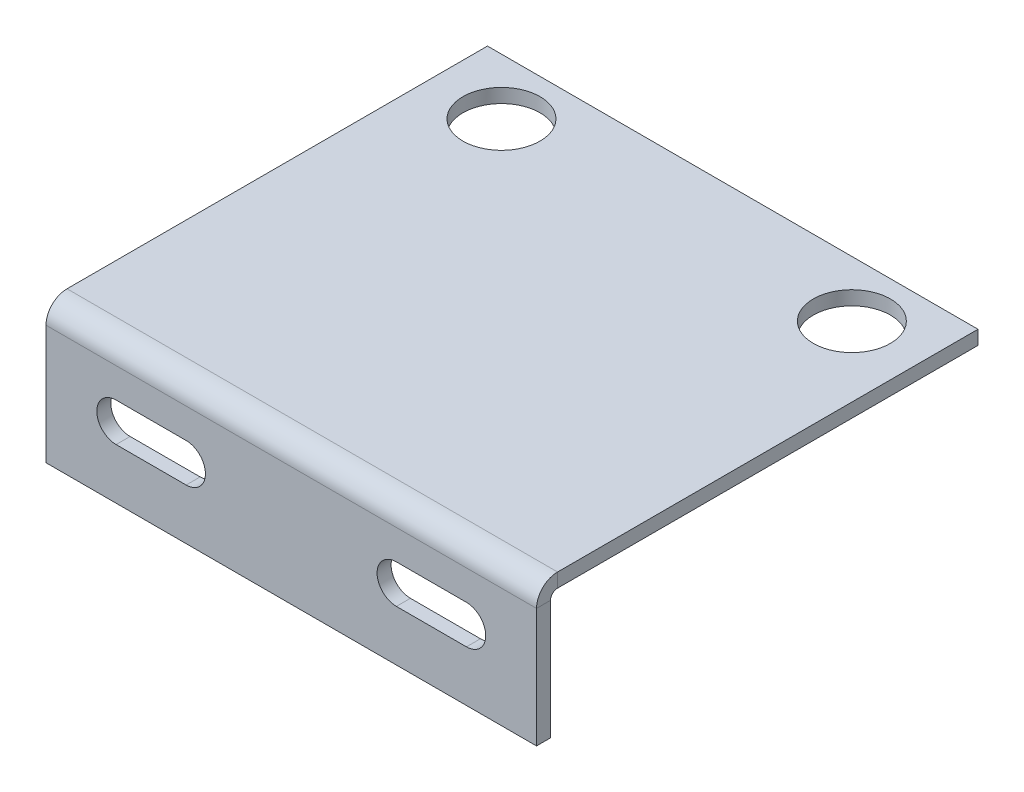
SolidWorks part; units mm, degrees
note: The reader was unsure of these and kept them because the rebuilt part matched: flange length of "边线-法兰1".
ref_plane "前视基准面" through (0, 0, 0) normal (0, 0, 1) x (1, 0, 0)
ref_plane "上视基准面" through (0, 0, 0) normal (0, 1, 0) x (1, 0, 0)
ref_plane "右视基准面" through (0, 0, 0) normal (1, 0, 0) x (0, 0, -1)
sketch "草图1" plane through (0, 0, 0) normal (0, 1, 0) x (1, 0, 0)
  line L1 (0, 0) -> (70, 0)
  line L2 (0, 0) -> (0, 60)
  line L3 (0, 60) -> (70, 60)
  line L4 (70, 0) -> (70, 60)
  dimension "D1" = 70
  dimension "D2" = 60
base flange "基体-法兰1" sketch "草图1" thickness 2 reverse thickness direction no parameters "D1"=1
edge flange "边线-法兰1" sketch "草图11" flange angle 90 flange length 20 flange position bend outside bend radius 1 thickness 2 relief rectangular parameters "D6"=10
bend "边线折弯1" bend radius 1 bend angle 90 parameters "D5"=1
sketch "草图11" plane through (0, -2, 0) normal (0, 0, 1) x (-1, 0, 0)
  line L0 (0, 0) -> (-70, 0) construction
  line L1 (0, 0) -> (-70, 0)
  line L2 (-70, 0) -> (-70, 18)
  line L3 (-70, 18) -> (0, 18)
  line L4 (0, 18) -> (0, 0)
sketch "草图12" plane through (0, 0, 1) normal (0, 0, -1) x (-1, 0, 0)
  line L0 (-55, -10) -> (-15, -10) construction
  line L1 (0, -20) -> (-70, -20) construction
  line L2 (-60, -10) -> (-50, -10) construction
  line L3 (-60, -7.25) -> (-50, -7.25)
  line L4 (-60, -12.75) -> (-50, -12.75)
  line L5 (-35, -10) -> (-35, -26.4916) construction
  line L6 (-10, -10) -> (-20, -10) construction
  line L7 (-10, -7.25) -> (-20, -7.25)
  line L8 (-10, -12.75) -> (-20, -12.75)
  arc A0 (-60, -7.25) -> (-60, -12.75) centre (-60, -10) ccw
  arc A1 (-50, -12.75) -> (-50, -7.25) centre (-50, -10) ccw
  arc A2 (-10, -7.25) -> (-10, -12.75) centre (-10, -10) cw
  arc A3 (-20, -12.75) -> (-20, -7.25) centre (-20, -10) cw
  point P2 (-35, -10)
  point P5 (-35, -20)
  point P8 (-55, -10)
  point P17 (-15, -10)
  dimension "D1" = 40
  dimension "D2" = 0
  dimension "D3" = 10
  dimension "D4" = 0
  dimension "D5" = 10
  dimension "D6" = 5.5
extrude "切除-拉伸1" cut sketch "草图12" against normal blind 10 normal cut yes
sketch "草图13" plane through (0, 0, 0) normal (0, 1, 0) x (1, 0, 0)
  line L0 (10, 52) -> (60, 52) construction
  line L1 (70, 60) -> (0, 60) construction
  circle A0 centre (10, 52) radius 5.5
  circle A1 centre (60, 52) radius 5.5
  point P4 (35, 52)
  point P5 (35, 60)
  dimension "D3" = 11
  dimension "D4" = 50
  dimension "D1" = 8
  dimension "D2" = 0
extrude "切除-拉伸2" cut sketch "草图13" against normal blind 10 normal cut yes
sketch "折弯-线1" plane through (0, 0, 0) normal (0, 1, 0) x (1, 0, 0)
sketch "边界框1" plane through (0, 0, 0) normal (0, 1, 0) x (1, 0, 0)
sheet metal parameters "钣金6" thickness 2 parameters "D1"=1
flat pattern "平板型式6" [suppressed]
sketch "折弯-线2" plane through (0, 0, 0) normal (0, 1, 0) x (1, 0, 0)
sketch "边界框2" [suppressed] plane through (0, 0, 0) normal (0, 1, 0) x (1, 0, 0)
sheet metal parameters "钣金7" thickness 2 parameters "D1"=1
flat pattern "平板型式6" [suppressed]
sketch "折弯-线2" plane through (0, 0, 0) normal (0, 1, 0) x (1, 0, 0)
sketch "边界框2" [suppressed] plane through (0, 0, 0) normal (0, 1, 0) x (1, 0, 0)
bend of the flat pattern "展平-<边线折弯1>1"
sheet metal parameters "钣金8" thickness 2 parameters "D1"=1
flat pattern "平板型式6" [suppressed]
sketch "折弯-线2" plane through (0, 0, 0) normal (0, 1, 0) x (1, 0, 0)
sketch "边界框2" [suppressed] plane through (0, 0, 0) normal (0, 1, 0) x (1, 0, 0)
bend of the flat pattern "展平-<边线折弯1>1"
sheet metal parameters "钣金9" thickness 2 parameters "D1"=1
flat pattern "平板型式6" [suppressed]
sketch "折弯-线2" plane through (0, 0, 0) normal (0, 1, 0) x (1, 0, 0)
sketch "边界框2" [suppressed] plane through (0, 0, 0) normal (0, 1, 0) x (1, 0, 0)
bend of the flat pattern "展平-<边线折弯1>1"
